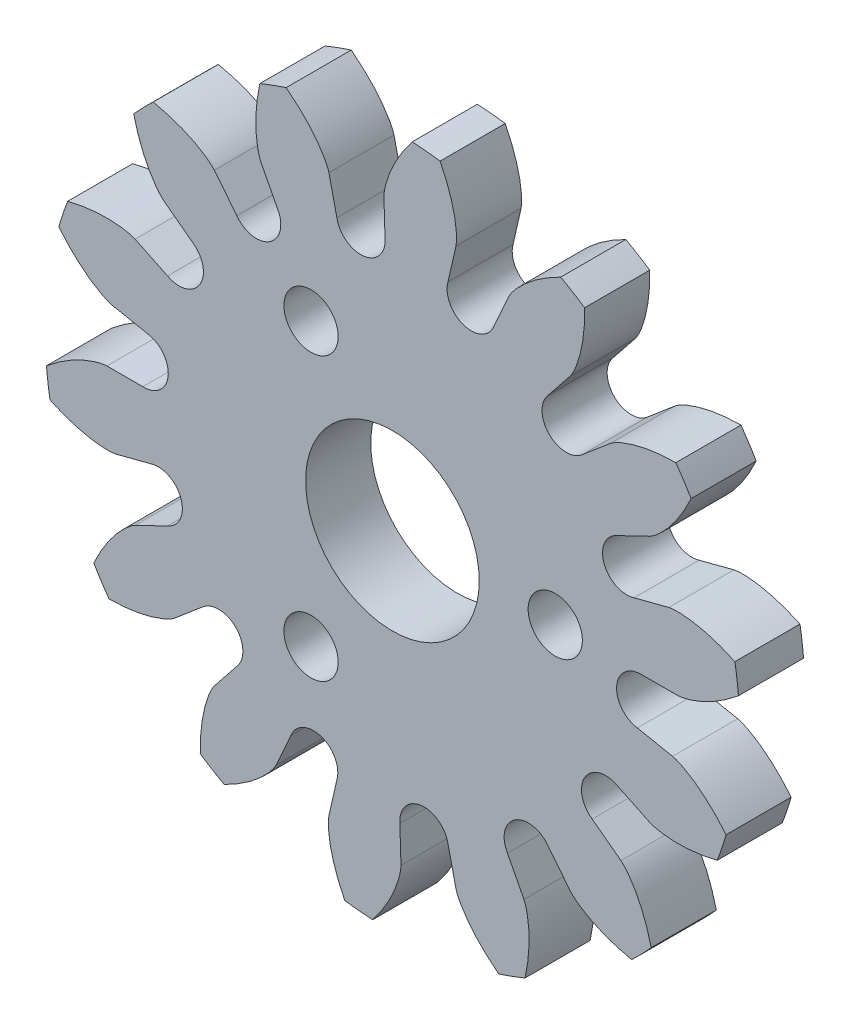
SolidWorks part; units mm, degrees
material "A2017"
ref_plane "正面" through (0, 0, 0) normal (0, 0, 1) x (1, 0, 0)
ref_plane "平面" through (0, 0, 0) normal (0, 1, 0) x (1, 0, 0)
ref_plane "右側面" through (0, 0, 0) normal (1, 0, 0) x (0, 0, -1)
sketch "歯車作図" plane through (0, 0, 0) normal (0, 0, 1) x (1, 0, 0)
  line L0 (0, 0) -> (11.5, 0) construction
  line L1 (11.5, 0) -> (13.1557, 0)
  line L2 (0, 0) -> (15.9243, -1.5543)
  circle A0 centre (0, 0) radius 16
  circle A1 centre (0, 0) radius 14 construction
  circle A2 centre (0, 0) radius 13.1557 construction
  circle A3 centre (0, 0) radius 11.5 construction
  arc A4 (13.9338, -1.36) -> (13.9984, 0.2086) centre (0, 0) ccw
  spline S0 degree 4 poles (13.1557, 0) (13.1962, 0.0018) (13.3095, 0.0121) (13.5229, 0.0532) (13.8623, 0.15) (14.2878, 0.3185) (14.8127, 0.5835) (15.3953, 0.9517) (15.9956, 1.4129) (16.5963, 1.9652) (17.1516, 2.5628) (17.6623, 3.1989) (18.1526, 3.9005) (18.7007, 4.8078) (19.264, 5.9401) (19.7932, 7.3107) (20.2281, 8.8843) (20.5168, 10.4909) (20.6662, 12.1159) (20.6828, 13.7479) (20.5733, 15.3756) (20.3435, 16.9914) (20.0435, 18.386) (19.7179, 19.5668) (19.4366, 20.4368) (19.2304, 21.0178) (19.0543, 21.4853) (18.8956, 21.8825) (18.7682, 22.1927) (18.6164, 22.5421) (18.4593, 22.8947) (18.2968, 23.2444) (18.0021, 23.8548) (17.7431, 24.3427) (17.4714, 24.849) (17.3291, 25.0891) (17.2373, 25.2512) knots 0 0 0 0 0 0.005604 0.015718 0.02996 0.048734 0.068727 0.096889 0.125051 0.153212 0.181374 0.209535 0.237696 0.271429 0.327752 0.384075 0.440398 0.496721 0.553044 0.609367 0.66569 0.722013 0.778336 0.806497 0.834659 0.84874 0.86282 0.876901 0.890982 0.900036 0.909091 0.931818 0.954545 0.977273 1 1 1 1 1 construction
  spline S1 degree 4 poles (13.1557, 0) (13.1962, 0.0018) (13.3095, 0.0121) (13.5229, 0.0532) (13.8623, 0.15) (14.2878, 0.3185) (14.8127, 0.5835) (15.3953, 0.9517) (15.9956, 1.4129) (16.5963, 1.9652) (17.1516, 2.5628) (17.6623, 3.1989) (18.1526, 3.9005) (18.7007, 4.8078) (19.264, 5.9401) (19.7932, 7.3107) (20.2281, 8.8843) (20.5168, 10.4909) (20.6662, 12.1159) (20.6828, 13.7479) (20.5733, 15.3756) (20.3435, 16.9914) (20.0435, 18.386) (19.7179, 19.5668) (19.4366, 20.4368) (19.2304, 21.0178) (19.0543, 21.4853) (18.8956, 21.8825) (18.7682, 22.1927) (18.6164, 22.5421) (18.5243, 22.7488) (18.475, 22.8577) (18.4502, 22.9118) knots 0 0 0 0 0 0.005604 0.015718 0.02996 0.048734 0.068727 0.096889 0.125051 0.153212 0.181374 0.209535 0.237696 0.271429 0.327752 0.384075 0.440398 0.496721 0.553044 0.609367 0.66569 0.722013 0.778336 0.806497 0.834659 0.84874 0.86282 0.876901 0.890982 0.900036 0.909091 0.909091 0.909091 0.909091 0.909091
  dimension "歯先円直径" = 32
  dimension "基礎ピッチ円直径" = 28
  dimension "基礎円直径" = 26.3114
  dimension "全歯丈" = 4.5
  dimension "基準ピッチ" = 1.5708
sketch "ｽｹｯﾁ1" plane through (0, 0, 0) normal (0, 0, 1) x (1, 0, 0)
  circle A0 centre (0, 0) radius 16 construction
  circle A1 centre (0, 0) radius 16
extrude "ﾎﾞｽ - 押し出し1" add sketch "ｽｹｯﾁ1" along normal mid plane 3
sketch "ｽｹｯﾁ3" plane through (0, 0, 1.5) normal (0, 0, 1) x (1, 0, 0)
  line L0 (11.5, 0) -> (13.1557, 0) construction
  line L1 (0, 0) -> (15.9243, -1.5543) construction
  line L2 (11.5, 0) -> (13.1557, 0)
  line L3 (11.4456, -1.1172) -> (15.9243, -1.5543)
  arc A0 (11.4456, -1.1172) -> (11.5, 0) centre (0, 0) ccw
  circle A1 centre (0, 0) radius 16
  arc A2 (15.9243, -1.5543) -> (15.9399, 1.3859) centre (0, 0) ccw
  spline S0 degree 4 poles (4.1667, 1999.9426) (5.2176, 54.9449) (8.5586, 1.0334) (11.432, -0.543) (13.8623, 0.15) (14.2878, 0.3185) (14.8127, 0.5835) (15.3953, 0.9517) (15.9956, 1.4129) (16.5963, 1.9652) (17.1516, 2.5628) (17.6623, 3.1989) (18.1526, 3.9005) (18.7007, 4.8078) (19.264, 5.9401) (19.7932, 7.3107) (20.2281, 8.8843) (20.5168, 10.4909) (20.6662, 12.1159) (20.6828, 13.7479) (20.5733, 15.3756) (20.3435, 16.9914) (20.0435, 18.386) (19.7179, 19.5668) (19.4366, 20.4368) (19.2304, 21.0178) (19.0543, 21.4853) (18.8956, 21.8825) (18.7682, 22.1927) (17.5787, 24.9297) (18.0275, 23.3017) (8.0916, 43.7385) (-815.1347, 1840.7278) knots -0.300203 -0.300203 -0.300203 -0.300203 -0.300203 0.005604 0.015718 0.02996 0.048734 0.068727 0.096889 0.125051 0.153212 0.181374 0.209535 0.237696 0.271429 0.327752 0.384075 0.440398 0.496721 0.553044 0.609367 0.66569 0.722013 0.778336 0.806497 0.834659 0.84874 0.86282 0.876901 0.890982 0.900036 1.225312 1.225312 1.225312 1.225312 1.225312 only from (13.1557, 0) to (18.4502, 22.9118) construction
  spline S1 degree 4 poles (13.1557, 0) (13.1962, 0.0018) (13.3095, 0.0121) (13.5229, 0.0532) (13.8623, 0.15) (14.2878, 0.3185) (14.8127, 0.5835) (15.2963, 0.8892) (15.6468, 1.1478) (15.873, 1.3305) (15.9399, 1.3859) knots 0 0 0 0 0 0.005604 0.015718 0.02996 0.048734 0.068727 0.096889 0.108898 0.108898 0.108898 0.108898 0.108898
  dimension "D1" = 0
extrude "ｶｯﾄ - 押し出し1" cut sketch "ｽｹｯﾁ3" against normal through all
pattern_circular "円形ﾊﾟﾀｰﾝ4" count 14 over 360 about axis through (0, 0, 1.5) along (0, 0, -1) of "ｶｯﾄ - 押し出し1"
mirror "ﾐﾗｰ1" about plane through (11.4456, -1.1172, -1.5) normal (-0.0971, -0.9953, 0) of "円形ﾊﾟﾀｰﾝ4", "ｶｯﾄ - 押し出し1"
sketch "ｽｹｯﾁ5" plane through (0, 0, 1.5) normal (0, 0, 1) x (1, 0, 0)
  circle A0 centre (0, 0) radius 4
  dimension "D1" = 8
extrude "ｶｯﾄ - 押し出し3" cut sketch "ｽｹｯﾁ5" against normal through all
hole_wizard "M3 ねじ穴1" positions "ｽｹｯﾁ6" profile "ｽｹｯﾁ7" tap size "M3" standard "JIS" end condition through all
sketch "ｽｹｯﾁ6" plane through (0, 0, 1.5) normal (0, 0, 1) x (1, 0, 0)
  line L0 (7.5, 0) -> (0, 0) construction
  circle A0 centre (0, 0) radius 7.5
  point P0 (7.5, 0)
  dimension "D1" = 15
sketch "ｽｹｯﾁ7" plane through (7.5, 0, 1.5) normal (1, 0, 0) x (0, -1, 0)
  line L0 (0, 0) -> (0, 3)
  line L1 (0, 3) -> (1.25, 3)
  line L2 (1.25, 3) -> (1.25, 0)
  line L5 (1.25, 0) -> (0, 0)
  line L11 (0, -6.35) -> (0, 107.95) construction
  dimension "次ｻｰﾌｪｽまでのねじ下穴ﾄﾞﾘﾙ直径" = 2.5
  dimension "次ｻｰﾌｪｽまでのねじ下穴ﾄﾞﾘﾙの深さ" = 3
cosmetic thread "穴のねじ山1" parameters "D2"=3
pattern_circular "円形ﾊﾟﾀｰﾝ6" count 3 over 360 about axis through (0, 0, -1.5) along (0, 0, 1) of "M3 ねじ穴1"
sketch "ｽｹｯﾁ8" plane through (0, 0, 1.5) normal (0, 0, 1) x (1, 0, 0)
  circle A0 centre (3.6361, 10.91) radius 1.1185
  arc A1 (4.6787, 10.5052) -> (2.559, 11.2117) centre (0, 0) ccw construction
  circle A2 centre (8.0097, 8.252) radius 1.1185
  circle A3 centre (10.7969, 3.9595) radius 1.1185
  circle A4 centre (11.4456, -1.1172) radius 1.1185
  circle A5 centre (9.8274, -5.9726) radius 1.1185
  circle A6 centre (6.2628, -9.6451) radius 1.1185
  circle A7 centre (1.4577, -11.4072) radius 1.1185
  circle A8 centre (-3.6361, -10.91) radius 1.1185
  circle A9 centre (-8.0097, -8.252) radius 1.1185
  circle A10 centre (-10.7969, -3.9595) radius 1.1185
  circle A11 centre (-11.4456, 1.1172) radius 1.1185
  circle A12 centre (-9.8274, 5.9726) radius 1.1185
  circle A13 centre (-6.2628, 9.6451) radius 1.1185
  circle A14 centre (-1.4577, 11.4072) radius 1.1185
  point P6 (0, 0)
  point P34 (0, 0)
  dimension "D1" = 14
extrude "ｶｯﾄ - 押し出し4" cut sketch "ｽｹｯﾁ8" against normal through all
equation "\"モジュール\"= 2"
equation "\"歯数\"= 14"
equation "\"圧力角\"= 20"
equation "\"歯先円直径@歯車作図\" =  ( \"歯数\" + 2 )  * \"モジュール\""
equation "\"基礎ピッチ円直径@歯車作図\" = \"モジュール\" * \"歯数\""
equation "\"基礎円直径@歯車作図\" = \"歯数\" * \"モジュール\" * cos ( \"圧力角\" ) "
equation "\"全歯丈@歯車作図\" = 2.25 * \"モジュール\""
equation "\"基準ピッチ@歯車作図\" = PI * \"モジュール\" / 4"
equation "\"D1@円形ﾊﾟﾀｰﾝ4\"=\"歯数\""
